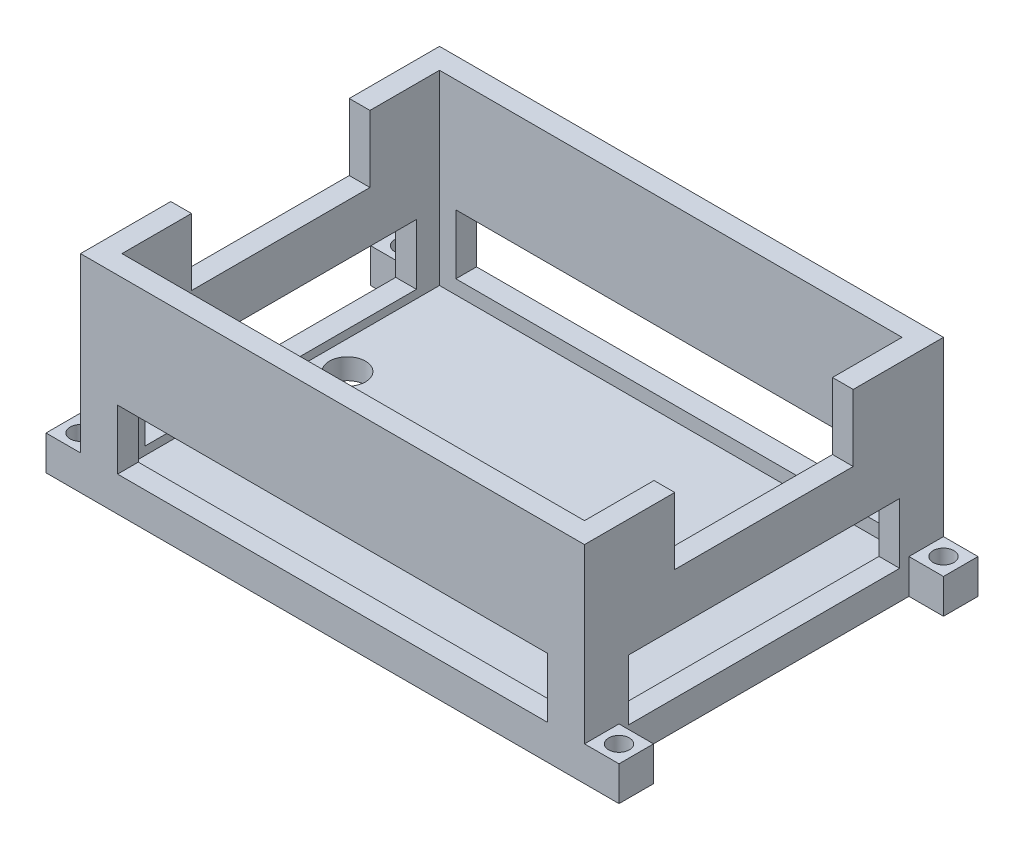
SolidWorks part; units mm, degrees
ref_plane "前视基准面" through (0, 0, 0) normal (0, 0, 1) x (1, 0, 0)
ref_plane "上视基准面" through (0, 0, 0) normal (0, 1, 0) x (1, 0, 0)
ref_plane "右视基准面" through (0, 0, 0) normal (1, 0, 0) x (0, 0, -1)
other "Configuration Table"
sketch "草图1" plane through (0, 0, 0) normal (0, 1, 0) x (1, 0, 0)
  line L0 (-36.5, 26) -> (36.5, 26)
  line L1 (-33.5, 23) -> (33.5, 23)
  line L2 (-33.5, 23) -> (-33.5, -23)
  line L3 (-33.5, -23) -> (33.5, -23)
  line L4 (33.5, 23) -> (33.5, -23)
  line L5 (-33.5, 23) -> (33.5, -23) construction
  line L6 (-33.5, -23) -> (33.5, 23) construction
  line L11 (36.5, 26) -> (36.5, -26)
  line L12 (-36.5, -26) -> (36.5, -26)
  line L13 (-36.5, 26) -> (-36.5, -26)
  point P0 (0, 0)
  dimension "D1" = 67
  dimension "D2" = 46
  dimension "D3" = 3
extrude "凸台-拉伸1" add sketch "草图1" along normal blind 30
extrude "凸台-拉伸2" add sketch "草图1<2>" along normal blind 3 contours L4 L1 L2 L3 region at (0, 0, 0)
sketch "草图1<2>" plane through (0, 0, 0) normal (0, 1, 0) x (1, 0, 0) same geometry as "草图1"
sketch "草图2" plane through (0, 0, -23) normal (0, 0, 1) x (1, 0, 0)
  line L0 (0, 0) -> (0, 40.9834) construction
  line L1 (-31.1343, 13.6792) -> (31.1343, 13.6792)
  line L2 (-31.1343, 13.6792) -> (-31.1343, 5.0218)
  line L3 (-31.1343, 5.0218) -> (31.1343, 5.0218)
  line L4 (31.1343, 13.6792) -> (31.1343, 5.0218)
extrude "切除-拉伸1" cut sketch "草图2" against normal through all both and the other way through all
sketch "草图3" plane through (0, 0, 0) normal (0, 1, 0) x (1, 0, 0)
  line L0 (36.5, 26) -> (41.5, 26)
  line L1 (41.5, 26) -> (41.5, 21)
  line L2 (41.5, 21) -> (36.5, 21)
  line L3 (36.5, -26) -> (36.5, 26) construction
  line L4 (36.5, 21) -> (36.5, 26)
  line L5 (0, 0) -> (95.9132, 0) construction
  line L6 (0, 0) -> (0, 67.5452) construction
  line L7 (41.5, -21) -> (36.5, -21)
  line L8 (41.5, -26) -> (41.5, -21)
  line L9 (36.5, -26) -> (41.5, -26)
  line L10 (36.5, -21) -> (36.5, -26)
  line L11 (-36.5, -21) -> (-36.5, -26)
  line L12 (-36.5, -26) -> (-41.5, -26)
  line L13 (-41.5, -26) -> (-41.5, -21)
  line L14 (-41.5, -21) -> (-36.5, -21)
  line L15 (-36.5, 21) -> (-36.5, 26)
  line L16 (-41.5, 21) -> (-36.5, 21)
  line L17 (-41.5, 26) -> (-41.5, 21)
  line L18 (-36.5, 26) -> (-41.5, 26)
  line L19 (-41.5, 26) -> (-36.5, 21) construction
  line L20 (-36.5, 26) -> (-41.5, 21) construction
  circle A0 centre (39, 23.5) radius 1.5
  circle A1 centre (39, -23.5) radius 1.5
  circle A2 centre (-39, -23.5) radius 1.5
  circle A3 centre (-39, 23.5) radius 1.5
  point P32 (-39, 23.5)
  dimension "D3" = 3
  dimension "D1" = 5
  dimension "D2" = 5
extrude "凸台-拉伸3" add sketch "草图3" along normal blind 5
sketch "草图4" plane through (33.5, 0, 0) normal (-1, 0, 0) x (0, 0, 1)
  line L0 (-19.6586, 4.1915) -> (-19.6586, 12.9557)
  line L1 (19.6586, 4.1915) -> (-19.6586, 4.1915)
  line L2 (0, 0) -> (0, 34.6379) construction
  line L3 (-19.6586, 12.9557) -> (19.6586, 12.9557)
  line L4 (19.6586, 12.9557) -> (19.6586, 4.1915)
extrude "切除-拉伸2" cut sketch "草图4" against normal through all both and the other way through all
sketch "草图5" plane through (36.5, 0, 0) normal (1, 0, 0) x (0, 0, -1)
  line L0 (0, 0) -> (0, 34.7572) construction
  line L1 (-12.9267, 30) -> (-12.9267, 20.3315)
  line L2 (-26, 30) -> (26, 30) construction
  line L3 (-12.9267, 20.3315) -> (12.9267, 20.3315)
  line L4 (12.9267, 20.3315) -> (12.9267, 30)
  line L5 (12.9267, 30) -> (-12.9267, 30)
extrude "切除-拉伸3" cut sketch "草图5" against normal through all both and the other way through all
sketch "草图6" plane through (0, 3, 0) normal (0, 1, 0) x (1, 0, 0)
  circle A1 centre (-29.3789, 5.5389) radius 2.6137
extrude "切除-拉伸4" cut sketch "草图6" against normal through all
